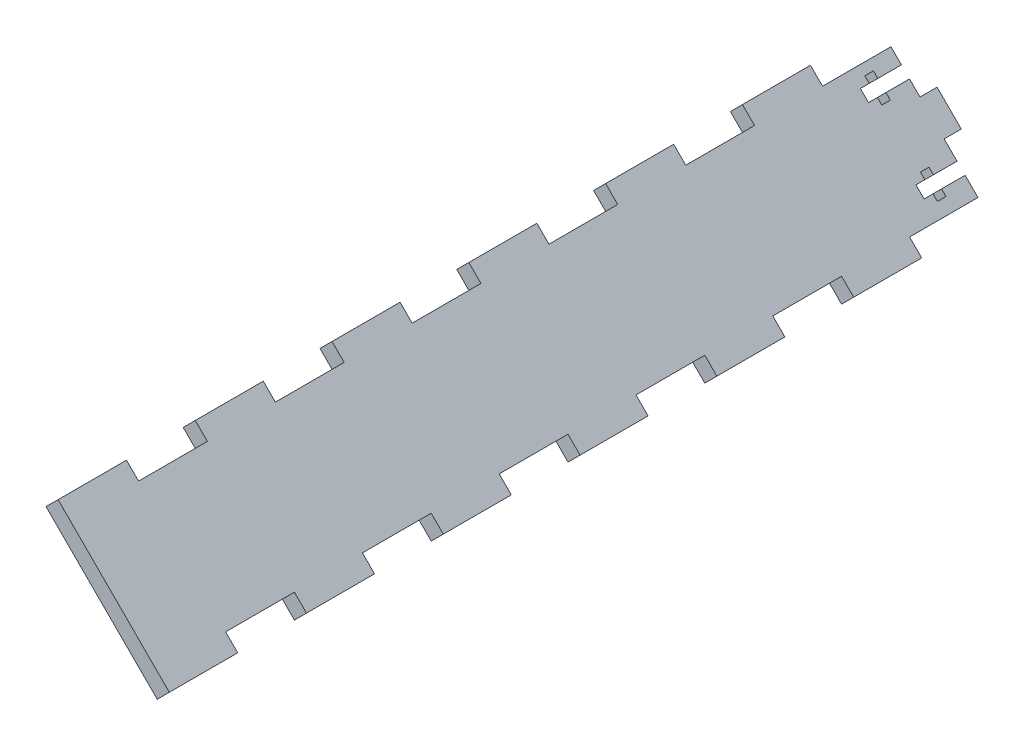
SolidWorks part; units mm, degrees
ref_plane "Front Plane" through (0, 0, 0) normal (0, 0, 1) x (1, 0, 0)
ref_plane "Top Plane" through (0, 0, 0) normal (0, 1, 0) x (1, 0, 0)
ref_plane "Right Plane" through (0, 0, 0) normal (1, 0, 0) x (0, 0, -1)
sketch "Sketch1" plane through (0, 0, 0) normal (0, 0, 1) x (1, 0, 0)
  line L0 (66.9029, 45.85) -> (108.2121, 4.5408)
  line L1 (66.9029, 45.85) -> (71.393, 50.3401)
  line L2 (108.2121, 4.5408) -> (112.7022, 9.0309)
  line L3 (71.393, 50.3401) -> (112.7022, 9.0309)
  line L4 (76.7812, -26.8901) -> (72.2911, -22.4) construction
extrude "Boss-Extrude1" add sketch "Sketch1" along normal up to surface (304.8 mm away)
sketch "Sketch2" plane through (60.8666, 60.8666, 0) normal (0.7071, 0.7071, 0) x (0, 0, -1)
  line L0 (-304.8, -14.8867) -> (0, -14.8867) construction
  line L1 (-279.4, -21.2367) -> (-253.8574, -21.2367)
  line L2 (-279.4, -21.2367) -> (-279.4, -14.8867)
  line L3 (-279.4, -14.8867) -> (-253.8574, -14.8867)
  line L4 (-253.8574, -21.2367) -> (-253.8574, -14.8867)
  line L5 (-304.8, -73.3067) -> (0, -73.3067) construction
  line L6 (-279.4, -66.9567) -> (-253.8574, -66.9567)
  line L7 (-279.4, -66.9567) -> (-279.4, -73.3067)
  line L8 (-279.4, -73.3067) -> (-253.8574, -73.3067)
  line L9 (-253.8574, -66.9567) -> (-253.8574, -73.3067)
extrude "Cut-Extrude1" cut sketch "Sketch2" against normal blind 6.35
pattern_linear "LPattern1" count 6 spacing 50.8 along (0, 0, -1) of "Cut-Extrude1"
sketch "Sketch3" plane through (0, 0, 0) normal (0, 0, -1) x (-1, 0, 0)
  line L0 (-82.1811, 30.5718) -> (-91.1613, 21.5915)
  line L1 (-71.393, 41.3598) -> (-103.722, 9.0309) construction
  line L2 (-91.1613, 21.5915) -> (-95.6515, 26.0817)
  line L3 (-108.2121, 13.521) -> (-75.8832, 45.85) construction
  line L4 (-95.6515, 26.0817) -> (-86.6712, 35.0619)
  line L5 (-86.6712, 35.0619) -> (-82.1811, 30.5718)
  dimension "D1" = 21.6066
  dimension "D2" = 12.7
extrude "Boss-Extrude2" add sketch "Sketch3" along normal blind 6.35
sketch "Sketch4" plane through (56.3764, 56.3764, 0) normal (-0.7071, -0.7071, 0) x (-0.7071, 0.7071, 0)
  line L0 (-28.865, -4.261) -> (-28.865, -30.7468) construction
  line L1 (-58.075, -4.261) -> (-58.075, -30.7468) construction
  line L2 (-66.9567, 0) -> (-66.9567, -25.4) construction
  line L3 (-49.1933, 6.35) -> (-49.1933, 0) construction
  line L4 (-36.4933, 6.35) -> (-36.4933, 0) construction
  line L5 (-21.2367, -25.4) -> (-21.2367, 0) construction
  line L6 (-49.1933, 0) -> (-66.9567, 0) construction
  line L7 (-21.2367, 0) -> (-36.4933, 0) construction
  line B0 (-55.9414, 0) -> (-60.2086, 0)
  line B1 (-60.2086, -11.938) -> (-62.52, -11.938)
  line B2 (-62.52, -11.938) -> (-62.52, -8.763)
  line B3 (-62.52, -8.763) -> (-60.2086, -8.763)
  line B4 (-60.2086, -8.763) -> (-60.2086, 0)
  line B5 (-60.2086, -11.938) -> (-60.2086, -15.24)
  line B6 (-60.2086, -15.24) -> (-55.9414, -15.24)
  line B7 (-55.9414, -11.938) -> (-55.9414, -15.24)
  line B8 (-55.9414, -8.763) -> (-55.9414, 0)
  line B9 (-53.63, -8.763) -> (-55.9414, -8.763)
  line B10 (-53.63, -11.938) -> (-53.63, -8.763)
  line B11 (-55.9414, -11.938) -> (-53.63, -11.938)
  line B12 (-26.7314, 0) -> (-30.9986, 0)
  line B13 (-30.9986, -11.938) -> (-33.31, -11.938)
  line B14 (-33.31, -11.938) -> (-33.31, -8.763)
  line B15 (-33.31, -8.763) -> (-30.9986, -8.763)
  line B16 (-30.9986, -8.763) -> (-30.9986, 0)
  line B17 (-30.9986, -11.938) -> (-30.9986, -15.24)
  line B18 (-30.9986, -15.24) -> (-26.7314, -15.24)
  line B19 (-26.7314, -11.938) -> (-26.7314, -15.24)
  line B20 (-26.7314, -8.763) -> (-26.7314, 0)
  line B21 (-24.42, -8.763) -> (-26.7314, -8.763)
  line B22 (-24.42, -11.938) -> (-24.42, -8.763)
  line B23 (-26.7314, -11.938) -> (-24.42, -11.938)
sketch_block_instance "TSlot-1"
sketch_block "TSlot" parameters "D1"=3.302, "D2"=3.175
sketch_block_instance "TSlot-2"
extrude "Cut-Extrude2" cut sketch "Sketch4" against normal through all
